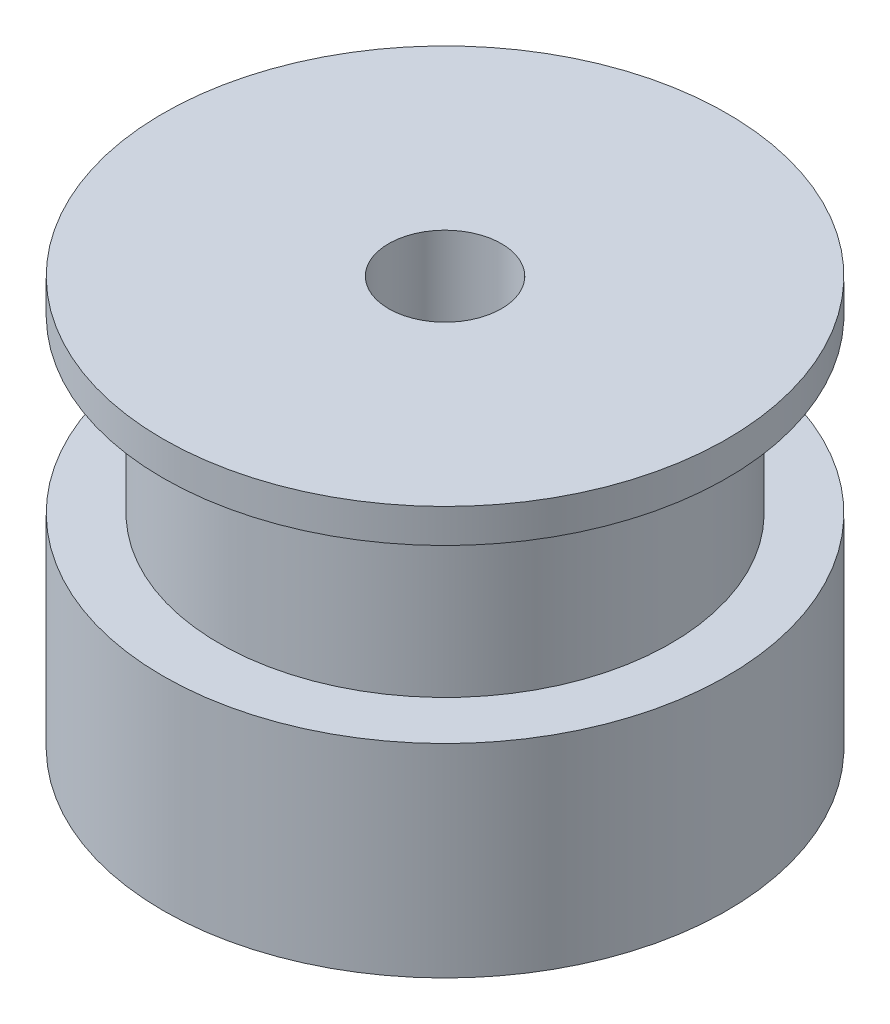
SolidWorks part; units mm, degrees
material "6061 Alloy"
ref_plane "Front Plane" through (0, 0, 0) normal (0, 0, 1) x (1, 0, 0)
ref_plane "Top Plane" through (0, 0, 0) normal (0, 1, 0) x (1, 0, 0)
ref_plane "Right Plane" through (0, 0, 0) normal (1, 0, 0) x (0, 0, -1)
sketch "Sketch1" plane through (0, 0, 0) normal (0, 1, 0) x (1, 0, 0)
  circle A0 centre (0, 0) radius 12.5
  dimension "D1" = 25
extrude "Boss-Extrude1" add sketch "Sketch1" along normal blind 9
sketch "Sketch2" plane through (0, 9, 0) normal (0, 1, 0) x (1, 0, 0)
  circle A0 centre (0, 0) radius 10
  dimension "D1" = 20
extrude "Boss-Extrude2" add sketch "Sketch2" along normal blind 7.6
sketch "Sketch3" plane through (0, 16.6, 0) normal (0, 1, 0) x (1, 0, 0)
  circle A0 centre (0, 0) radius 12.5
  dimension "D1" = 25
extrude "Boss-Extrude3" add sketch "Sketch3" along normal blind 1.5
sketch "Sketch4" plane through (0, 18.1, 0) normal (0, 1, 0) x (1, 0, 0)
  circle A0 centre (0, 0) radius 2.5
  dimension "D1" = 5
extrude "Cut-Extrude1" cut sketch "Sketch4" against normal through all
